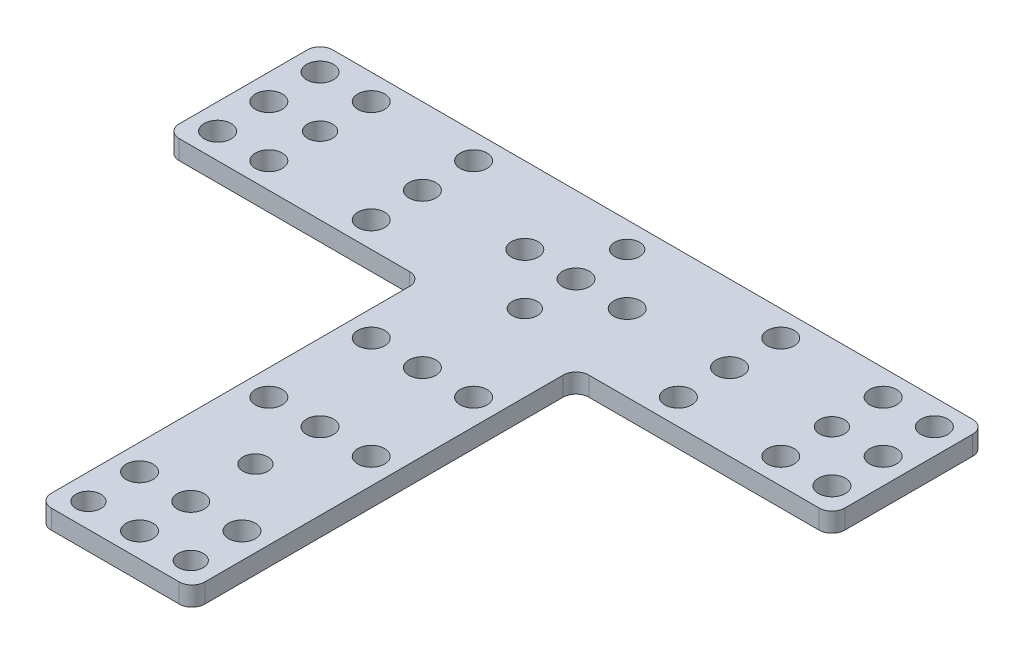
SolidWorks part; units mm, degrees
ref_plane "Front Plane" through (0, 0, 0) normal (0, 0, 1) x (1, 0, 0)
ref_plane "Top Plane" through (0, 0, 0) normal (0, 1, 0) x (1, 0, 0)
ref_plane "Right Plane" through (0, 0, 0) normal (1, 0, 0) x (0, 0, -1)
sketch "Sketch1" plane through (0, 0, 0) normal (0, 1, 0) x (1, 0, 0)
  line L0 (12, 0) -> (52, 0)
  line L1 (-52, 24) -> (52, 24)
  line L2 (-52, 24) -> (-52, 0)
  line L3 (-52, 0) -> (-12, 0)
  line L4 (52, 24) -> (52, 0)
  line L6 (-12, 0) -> (-12, -60)
  line L7 (-12, -60) -> (12, -60)
  line L8 (12, 0) -> (12, -60)
  point P10 (0, 24)
  dimension "D1" = 24
  dimension "D2" = 24
  dimension "D3" = 84
  dimension "D4" = 104
extrude "Boss-Extrude1" add sketch "Sketch1" along normal blind 3
sketch "Sketch2" plane through (0, 3, 0) normal (0, 1, 0) x (1, 0, 0)
  line L0 (-52, 12) -> (52, 12) construction
  line L1 (-52, 24) -> (-52, 0) construction
  line L2 (52, 0) -> (52, 24) construction
  line L3 (0, 24) -> (0, -60) construction
  line L4 (52, 24) -> (-52, 24) construction
  line L5 (-12, -60) -> (12, -60) construction
  line L6 (-52, 20) -> (52, 20) construction
  line L7 (-48, 12) -> (-48, 20) construction
  line L8 (-40, 20) -> (-40, 12) construction
  line L9 (-24, 12) -> (-24, 20) construction
  line L10 (-8, -60) -> (-8, 24) construction
  line L11 (-8, -12) -> (0, -12) construction
  line L12 (0, -28) -> (-8, -28) construction
  line L13 (-8, -48.2) -> (0, -48.2) construction
  line L14 (0, -56.2) -> (-8, -56.2) construction
  line L15 (24, 12) -> (24, 20) construction
  line L16 (40, 20) -> (40, 12) construction
  line L17 (48, 12) -> (48, 20) construction
  circle A0 centre (0, 12) radius 2.1
  circle A2 centre (-8, 12) radius 2.1
  circle A3 centre (0, 20) radius 1.95
  circle A4 centre (-48, 12) radius 2.1
  circle A5 centre (-48, 20) radius 2.1
  circle A6 centre (-40, 12) radius 1.95
  circle A7 centre (-40, 20) radius 2.1
  circle A8 centre (-24, 12) radius 2.1
  circle A9 centre (-24, 20) radius 2.1
  circle A10 centre (0, -12) radius 2.1
  circle A11 centre (0, -28) radius 2.1
  circle A12 centre (0, -38.1) radius 1.95
  circle A13 centre (0, -48.2) radius 2.1
  circle A14 centre (0, -56.2) radius 2.1
  circle A15 centre (-8, -56.2) radius 1.95
  circle A16 centre (-8, -48.2) radius 2.1
  circle A18 centre (-8, -28) radius 2.1
  circle A19 centre (-8, -12) radius 2.1
  circle A20 centre (0, 4) radius 1.95
  circle A21 centre (-24, 4) radius 2.1
  circle A22 centre (-40, 4) radius 2.1
  circle A23 centre (-48, 4) radius 2.1
  circle A24 centre (8, -56.2) radius 1.95
  circle A25 centre (8, -48.2) radius 2.1
  circle A26 centre (8, -28) radius 2.1
  circle A27 centre (8, -12) radius 2.1
  circle A28 centre (8, 12) radius 2.1
  circle A29 centre (24, 4) radius 2.1
  circle A30 centre (24, 20) radius 2.1
  circle A31 centre (24, 12) radius 2.1
  circle A32 centre (40, 20) radius 2.1
  circle A33 centre (40, 12) radius 1.95
  circle A34 centre (48, 12) radius 2.1
  circle A35 centre (40, 4) radius 2.1
  circle A36 centre (48, 4) radius 2.1
  circle A37 centre (48, 20) radius 2.1
  dimension "D1" = 4.2
  dimension "D6" = 3.9
  dimension "D4" = 16
  dimension "D8" = 16
  dimension "D2" = 8
  dimension "D3" = 16
  dimension "D5" = 16
  dimension "D7" = 16
  dimension "D9" = 8
  dimension "D10" = 24
  dimension "D11" = 16
  dimension "D12" = 16
  dimension "D13" = 8
extrude "Cut-Extrude1" cut sketch "Sketch2" against normal through all
fillet "Fillet1" radius 2 8 edges at (52, 1.5, -24) (52, 1.5, 0) (12, 1.5, 0) (12, 1.5, 60) (-12, 1.5, 60) (-12, 1.5, 0) (-52, 1.5, -24) (-52, 1.5, 0)
equation "\"width\"= 24"
equation "\"thk\"= 3"
equation "\"holesize\"= 4.2"
equation "\"holedistance\"= ( 20 + 12 ) / 2"
equation "\"D1@Sketch2\"=\"holesize\""
equation "\"D4@Sketch2\"=\"holedistance\""
equation "\"D2@Sketch2\"=\"holedistance\"/2"
equation "\"D3@Sketch2\"=\"holedistance\""
equation "\"D5@Sketch2\"=\"holedistance\""
equation "\"threaded_hole\"= 3.9"
equation "\"D6@Sketch2\"=\"threaded_hole\""
equation "\"D7@Sketch2\"=\"holedistance\""
equation "\"D9@Sketch2\"=\"holedistance\"/2"
equation "\"D10@Sketch2\"=\"holedistance\"*1.5"
equation "\"D11@Sketch2\"=\"holedistance\""
equation "\"D13@Sketch2\"=\"D12@Sketch2\"/2"
equation "\"fillet_radius\"= 2"
equation "\"D1@Fillet1\"=\"fillet_radius\""
